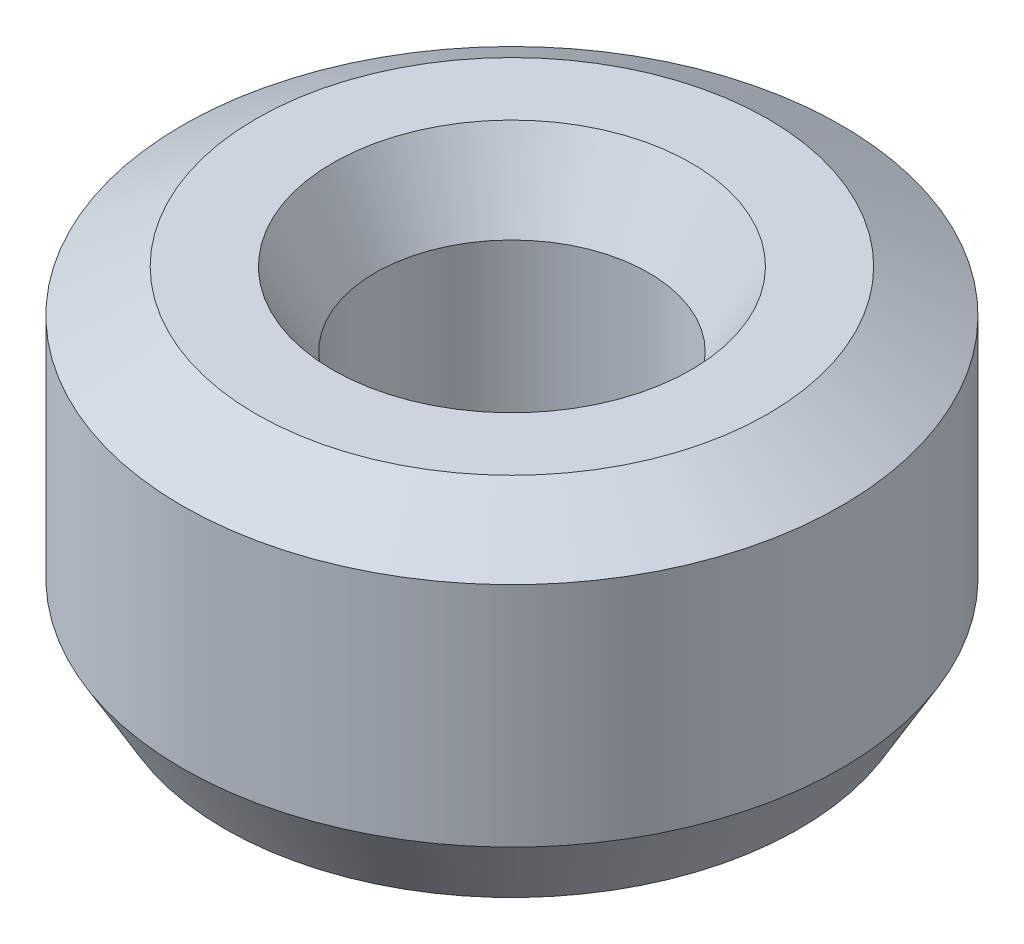
SolidWorks part; units mm, degrees
ref_plane "Front Plane" through (0, 0, 0) normal (0, 0, 1) x (1, 0, 0)
ref_plane "Top Plane" through (0, 0, 0) normal (0, 1, 0) x (1, 0, 0)
ref_plane "Right Plane" through (0, 0, 0) normal (1, 0, 0) x (0, 0, -1)
sketch "Sketch1" plane through (0, 0, 0) normal (0, 1, 0) x (1, 0, 0)
  circle A0 centre (0, 0) radius 22.5
  dimension "SLEEVE_OD" = 45
extrude "Boss-Extrude1" add sketch "Sketch1" along normal blind 23.4627
sketch "Sketch2" plane through (0, 0, 0) normal (0, 1, 0) x (1, 0, 0)
  circle A0 centre (0, 0) radius 9.3316
  dimension "BORE_D" = 18.6633
extrude "Cut-Extrude1" cut sketch "Sketch2" along normal through all
chamfer "Chamfer1" distance 2.9072 angle 60 4 edges at (0, 23.4627, 9.3316) (0, 0, 9.3316) (0, 0, 22.5) (0, 23.4627, 22.5) first distance on face at (0, 23.4627, 9.3316) first distance on face at (0, 0, 9.3316) first distance on face at (0, 23.4627, 22.5)
